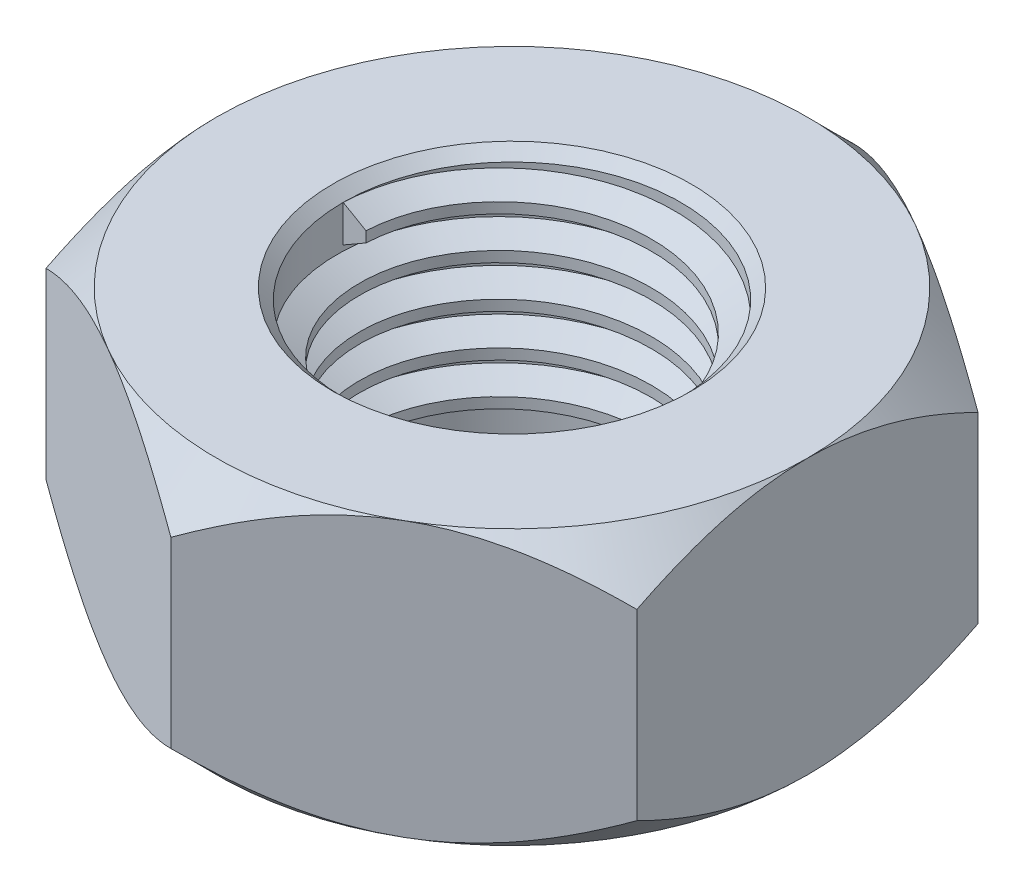
SolidWorks part; units mm, degrees
material "201 Annealed Stainless Steel (SS)"
ref_plane "Front Plane" through (0, 0, 0) normal (0, 0, 1) x (1, 0, 0)
ref_plane "Top Plane" through (0, 0, 0) normal (0, 1, 0) x (1, 0, 0)
ref_plane "Right Plane" through (0, 0, 0) normal (1, 0, 0) x (0, 0, -1)
sketch "Sketch1" plane through (0, 0, 0) normal (0, 1, 0) x (1, 0, 0)
  line L1 (0, 8.0829) -> (-7, 4.0415)
  line L2 (-7, 4.0415) -> (-7, -4.0415)
  line L3 (-7, -4.0415) -> (0, -8.0829)
  line L4 (0, -8.0829) -> (7, -4.0415)
  line L5 (7, -4.0415) -> (7, 4.0415)
  line L6 (7, 4.0415) -> (0, 8.0829)
  circle A0 centre (0, 0) radius 7 construction
  circle A1 centre (0, 0) radius 4
  dimension "D3" = 8
  dimension "D1" = 14
  dimension "D2" = 7
extrude "Boss-Extrude1" add sketch "Sketch1" along normal blind 3.25 and the other way blind 3.25
sketch "Sketch2" plane through (0, 3.25, 0) normal (0, 1, 0) x (1, 0, 0)
  circle A0 centre (0, 0) radius 7
extrude "Cut-Extrude1" cut sketch "Sketch2" against normal blind 6.5 draft 45 flip side to cut
mirror "Mirror2" about plane through (0, 0, 0) normal (0, 1, 0) of "Cut-Extrude1"
chamfer "Chamfer2" distance 0.25 angle 45 2 edges at (0, 3.25, 4) (0, -3.25, 4)
thread "Thread1" pitch 1 method extrude profile "Thread Profile1" start angle 0, offset 0, length 5, pitch 1, diameter 8
ref_plane "Plane1" through (-4, 3, 0) normal (0, 0, 1) x (-1, 0, 0)
sketch "Thread Profile1" plane through (-4, 3, 0) normal (0, 0, 1) x (-1, 0, 0)
  line L0 (0, 0) -> (0, 1) construction
  line L11 (0, 0) -> (0, 0.875)
  line L12 (0, 0.875) -> (-0.5413, 0.5625)
  line L13 (-0.5413, 0.5625) -> (-0.5413, 0.3125)
  line L15 (-0.5413, 0.3125) -> (0, 0)
  line L17 (-0.5413, 0.4375) -> (0, 0.4375) construction
  point P2 (0, 0)
  dimension "Pitch" = 1
  dimension "Profile_Angle" = 60
  dimension "Profile_Land" = 0.25
  dimension "Profile_Height" = 0.5413
